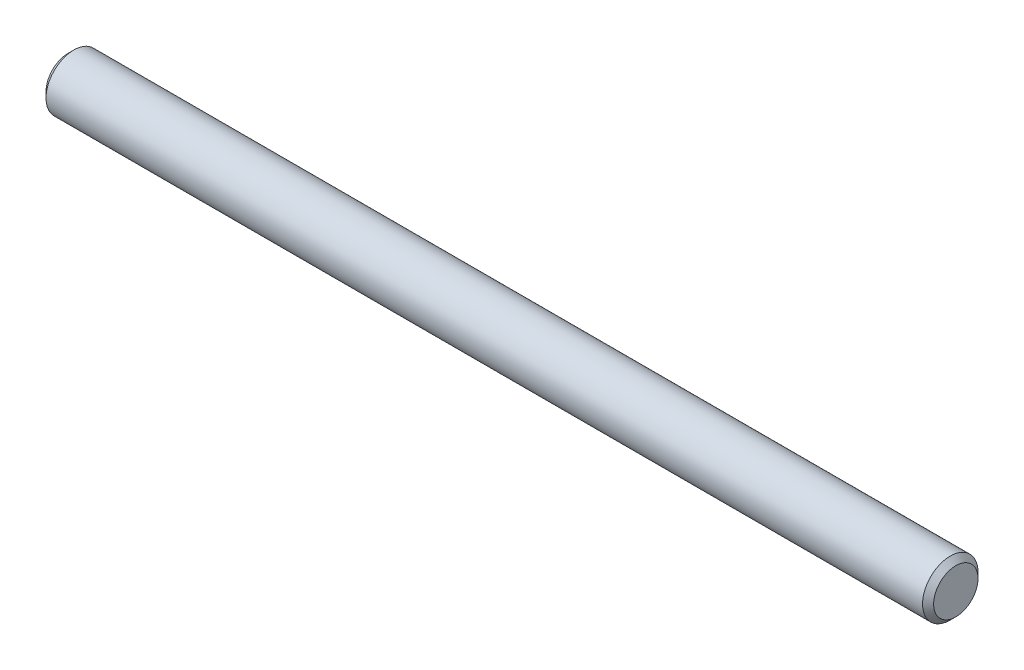
SolidWorks part; units mm, degrees
material "Plain Carbon Steel"
ref_plane "Front" through (0, 0, 0) normal (0, 0, 1) x (1, 0, 0)
ref_plane "Top" through (0, 0, 0) normal (0, 1, 0) x (1, 0, 0)
ref_plane "Right" through (0, 0, 0) normal (1, 0, 0) x (0, 0, -1)
sketch "Sketch1" plane through (0, 0, 0) normal (0, 0, 1) x (1, 0, 0)
  line L0 (-152.4, 0) -> (152.4, 0) construction
  line L1 (152.4, 9.525) -> (152.4, -9.525) construction
  line L2 (-152.4, 9.525) -> (-152.4, -9.525) construction
  dimension "Length" = 304.8
  dimension "Diameter" = 19.05
sketch "Sketch2" plane through (0, 0, 0) normal (1, 0, 0) x (0, 0, -1)
  circle A0 centre (0, 0) radius 9.525
extrude "Extrude1" add sketch "Sketch2" against normal up to vertex (152.4 mm away) and the other way up to vertex (152.4 mm away) up to point (-152.4, 9.525, 0) other way up to point (152.4, 9.525, 0)
chamfer "Chamfer1" distance 1.905 angle 45 2 edges at (152.4, 0, -9.525) (-152.4, 0, -9.525)
equation "\"D1@Chamfer1\" = \"Diameter@Sketch1\"*.1"
